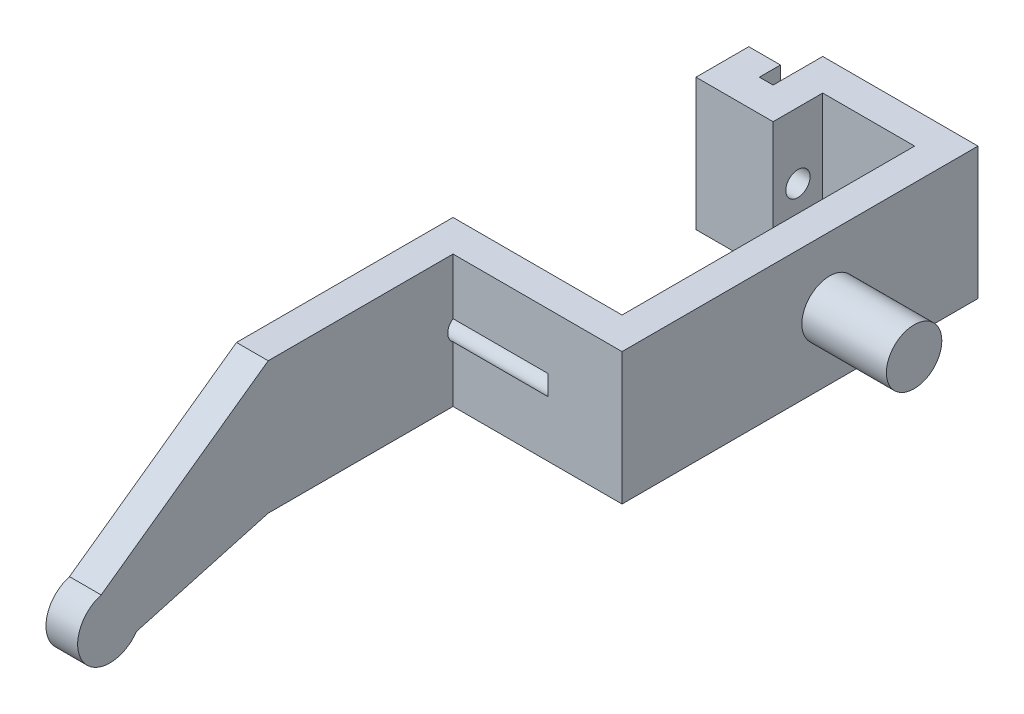
SolidWorks part; units mm, degrees
ref_plane "前视基准面" through (0, 0, 0) normal (0, 0, 1) x (1, 0, 0)
ref_plane "上视基准面" through (0, 0, 0) normal (0, 1, 0) x (1, 0, 0)
ref_plane "右视基准面" through (0, 0, 0) normal (1, 0, 0) x (0, 0, -1)
sketch "草图1" plane through (0, 0, 0) normal (0, 1, 0) x (1, 0, 0)
  line L0 (0, 0) -> (16, 0)
  line L1 (16, 0) -> (16, -23)
  line L2 (16, -23) -> (0, -23)
  line L3 (0, -23) -> (0, -61)
  line L4 (0, 0) -> (0, 5)
  line L5 (0, 5) -> (3, 5)
  line L6 (3, 5) -> (3, 3)
  line L7 (3, 3) -> (4.3, 3)
  line L8 (19, 3) -> (19, -26)
  line L9 (19, -26) -> (3, -26)
  line L10 (3, -26) -> (3, -61)
  line L11 (3, -61) -> (0, -61)
  line L12 (16, 3) -> (16, 4.7)
  line L13 (7.3, 3) -> (7.3, 4.7)
  line L14 (7.3, 4.7) -> (16, 4.7)
  line L15 (4.3, 3) -> (4.3, 7.7)
  line L16 (4.3, 7.7) -> (19, 7.7)
  line L17 (19, 7.7) -> (19, 3)
  line L18 (7.3, 3) -> (7.3, 0)
  line L19 (16, 3) -> (16, 0)
  line L20 (7.3, 3) -> (16, 3)
  point P3 (8, 0)
  dimension "D1" = 3
  dimension "D2" = 3
  dimension "D3" = 3
  dimension "D4" = 3
  dimension "D5" = 16
  dimension "D6" = 3
  dimension "D7" = 23
  dimension "D8" = 5
  dimension "D9" = 35
  dimension "D10" = 8.7
  dimension "D11" = 1.7
  dimension "D12" = 3
  dimension "D13" = 3
  dimension "D14" = 3
extrude "凸台-拉伸1" add sketch "草图1" along normal blind 12.5 contours L12 L19 L1 L2 L3 L11 L10 L9 L8 L17 L16 L15 L7 L6 L5 L4 L0 L18 L13 L14 region at (0.7128, 0, -2.5)
sketch "草图2" plane through (0, 0, 0) normal (-1, 0, 0) x (0, 0, 1)
  line L4 (23, 0) -> (61, 0)
  line L5 (61, 0) -> (61, 12.5)
  line L6 (23, 0) -> (61, 0)
  line L7 (23, 12.5) -> (23, 0)
  line L9 (61, 0) -> (61, 12.5)
  line L11 (23, 12.5) -> (23, 0)
  line L12 (-5, 0) -> (0, 0)
  line L13 (0, 0) -> (0, 12.5)
  line L14 (-5, 0) -> (0, 0)
  line L15 (-5, 12.5) -> (-5, 0)
  line L17 (0, 0) -> (0, 12.5)
  line L19 (-5, 12.5) -> (-5, 0)
  line L20 (61, 12.5) -> (23, 12.5)
  line L21 (61, 12.5) -> (23, 12.5)
  line L22 (0, 12.5) -> (-5, 12.5)
  line L23 (0, 12.5) -> (-5, 12.5)
  circle A0 centre (25.35, 6.25) radius 1.15
  circle A1 centre (-2.35, 6.25) radius 1.15
  dimension "D5" = 2.3
  dimension "D6" = 2.3
  dimension "D3" = 2.35
  dimension "D4" = 2.35
  dimension "D1" = 0
  dimension "D2" = 0
extrude "切除-拉伸1" cut sketch "草图2" against normal blind 12 contours A1 | A0 region at (0, 6.25, 25.35) region at (0, 6.25, -2.35)
sketch "草图3" plane through (19, 0, 0) normal (1, 0, 0) x (0, 0, -1)
  line L0 (5, 12.5) -> (5, 0) construction
  line L4 (-26, 0) -> (7.7, 0)
  line L5 (-26, 0) -> (7.7, 0)
  line L6 (7.7, 0) -> (7.7, 12.5)
  line L7 (-26, 12.5) -> (-26, 0)
  line L11 (-26, 12.5) -> (-26, 0)
  line L13 (7.7, 0) -> (7.7, 12.5)
  line L14 (7.7, 12.5) -> (-26, 12.5)
  line L15 (7.7, 12.5) -> (-26, 12.5)
  circle A0 centre (-6.35, 6.25) radius 2.625
  dimension "D3" = 5.25
  dimension "D2" = 11.35
  dimension "D1" = 0
extrude "凸台-拉伸2" add sketch "草图3" along normal blind 8 contours A0 region at (19, 6.25, 6.35)
sketch "草图4" plane through (3, 0, 0) normal (1, 0, 0) x (0, 0, -1)
  line L0 (-61, 0) -> (-43.5, 12.5)
  line L1 (-43.5, 0) -> (-55.9744, -3.4683)
  line L2 (-55.9744, -3.4683) -> (-61, 0)
  line L5 (-26, 0) -> (-26, 5.3013)
  line L6 (-26, 7.1987) -> (-26, 12.5)
  line L7 (-26, 12.5) -> (-61, 12.5)
  line L8 (-61, 12.5) -> (-61, 0)
  line L9 (-26, 12.5) -> (-61, 12.5)
  line L10 (-26, 0) -> (-26, 5.3013)
  line L11 (-26, 7.1987) -> (-26, 12.5)
  line L13 (-61, 12.5) -> (-61, 0)
  line L18 (-61, 0) -> (-26, 0)
  line L19 (-61, 0) -> (-26, 0)
  circle A0 centre (-58.4872, -1.7341) radius 3.0531
  arc A1 (-26, 7.1987) -> (-26, 5.3013) centre (-25.35, 6.25) ccw
  arc A2 (-26, 7.1987) -> (-26, 5.3013) centre (-25.35, 6.25) ccw
  line M13 (-61, 12.5) -> (-61, 0)
  dimension "D2" = 20
  dimension "D1" = 0
extrude "切除-拉伸2" cut sketch "草图4" against normal blind 8 contours A0 L0 M13 region at (3, 8.3511, 55.155)
extrude "凸台-拉伸3" add sketch "草图4<4>" against normal blind 3 contours L2 A0 | L2 A0 | A0 L1 region at (3, -1.2298, 57.4083) region at (3, -2.8006, 59.2232) region at (3, -1.1199, 51.5698)
sketch "草图4<4>" plane through (3, 0, 0) normal (1, 0, 0) x (0, 0, -1) same geometry as "草图4"
